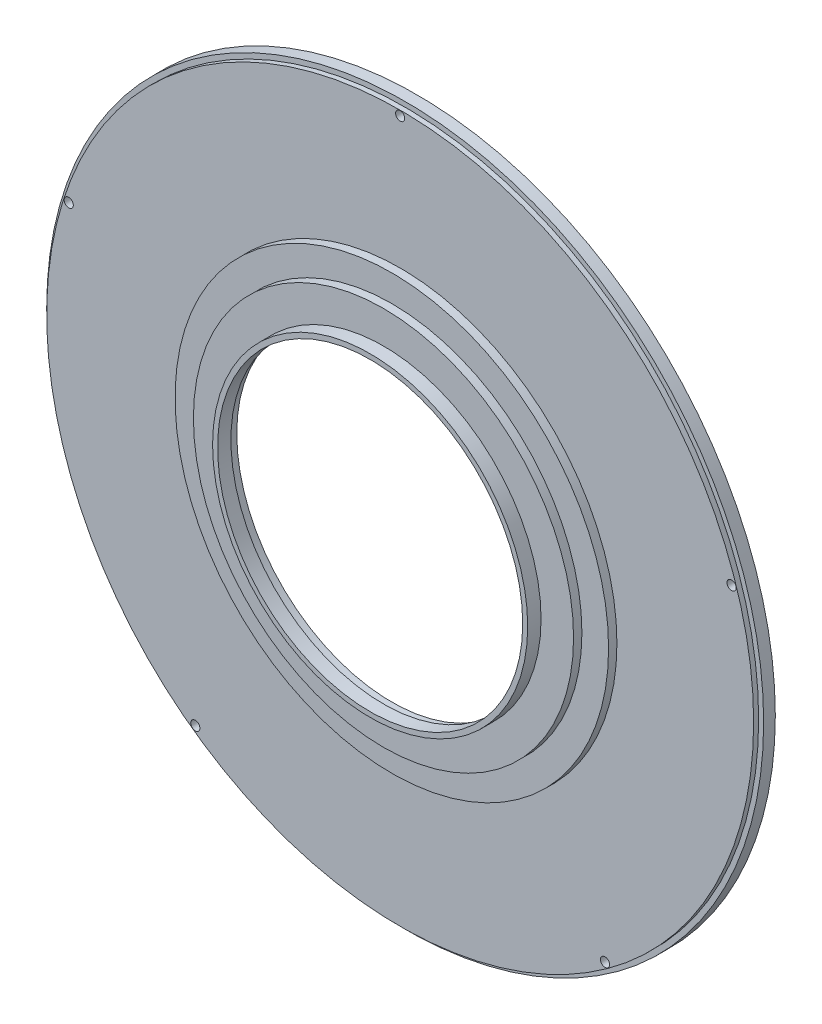
SolidWorks part; units mm, degrees
ref_plane "Front Plane" through (0, 0, 0) normal (0, 0, 1) x (1, 0, 0)
ref_plane "Top Plane" through (0, 0, 0) normal (0, 1, 0) x (1, 0, 0)
ref_plane "Right Plane" through (0, 0, 0) normal (1, 0, 0) x (0, 0, -1)
sketch "Sketch1" plane through (0, 0, 0) normal (0, 0, 1) x (1, 0, 0)
  circle A0 centre (0, 0) radius 215
  circle A1 centre (0, 0) radius 120
extrude "Plate" add sketch "Sketch1" along normal blind 10
ref_plane "Plane_z10" through (0, 0, 10) normal (0, 0, 1) x (1, 0, 0)
sketch "Sketch2" plane through (0, 0, 10) normal (0, 0, 1) x (1, 0, 0)
  circle A0 centre (0, 0) radius 130
  circle A1 centre (0, 0) radius 111
extrude "Bellmouth1" add sketch "Sketch2" along normal blind 5
ref_plane "Plane_z15" through (0, 0, 15) normal (0, 0, 1) x (1, 0, 0)
sketch "Sketch3" plane through (0, 0, 15) normal (0, 0, 1) x (1, 0, 0)
  circle A0 centre (0, 0) radius 114
  circle A1 centre (0, 0) radius 93
extrude "Bellmouth2" add sketch "Sketch3" along normal blind 5
ref_plane "Plane_z20" through (0, 0, 20) normal (0, 0, 1) x (1, 0, 0)
sketch "Sketch4" plane through (0, 0, 20) normal (0, 0, 1) x (1, 0, 0)
  circle A0 centre (0, 0) radius 94.5
  circle A1 centre (0, 0) radius 91.5
extrude "Bellmouth3" add sketch "Sketch4" along normal blind 8
sketch "Sketch5" plane through (0, 0, 0) normal (0, 0, 1) x (1, 0, 0)
  circle A0 centre (0, 0) radius 204
  circle A1 centre (0, 0) radius 144
extrude "Comb_groove" cut sketch "Sketch5" along normal blind 4
ref_plane "Plane_z7" through (0, 0, 7) normal (0, 0, 1) x (1, 0, 0)
sketch "Sketch6" plane through (0, 0, 7) normal (0, 0, 1) x (1, 0, 0)
  circle A0 centre (0, 0) radius 216
  circle A1 centre (0, 0) radius 212
extrude "Band_rabbet" cut sketch "Sketch6" along normal blind 3
sketch "Sketch7" plane through (0, 0, 0) normal (0, 0, 1) x (1, 0, 0)
  circle A0 centre (198.7708, 64.5846) radius 2.75
  circle A1 centre (0, 209) radius 2.75
  circle A2 centre (-198.7708, 64.5846) radius 2.75
  circle A3 centre (-122.8471, -169.0846) radius 2.75
  circle A4 centre (122.8471, -169.0846) radius 2.75
extrude "Rod_holes" cut sketch "Sketch7" along normal blind 10
sketch "Sketch8" plane through (0, 0, 0) normal (0, 0, 1) x (1, 0, 0)
  circle A0 centre (77.8815, 107.1948) radius 1.25
  circle A1 centre (-77.8815, 107.1948) radius 1.25
  circle A2 centre (-126.015, -40.9448) radius 1.25
  circle A3 centre (0, -132.5) radius 1.25
  circle A4 centre (126.015, -40.9448) radius 1.25
extrude "Spider_screws" cut sketch "Sketch8" along normal blind 8
